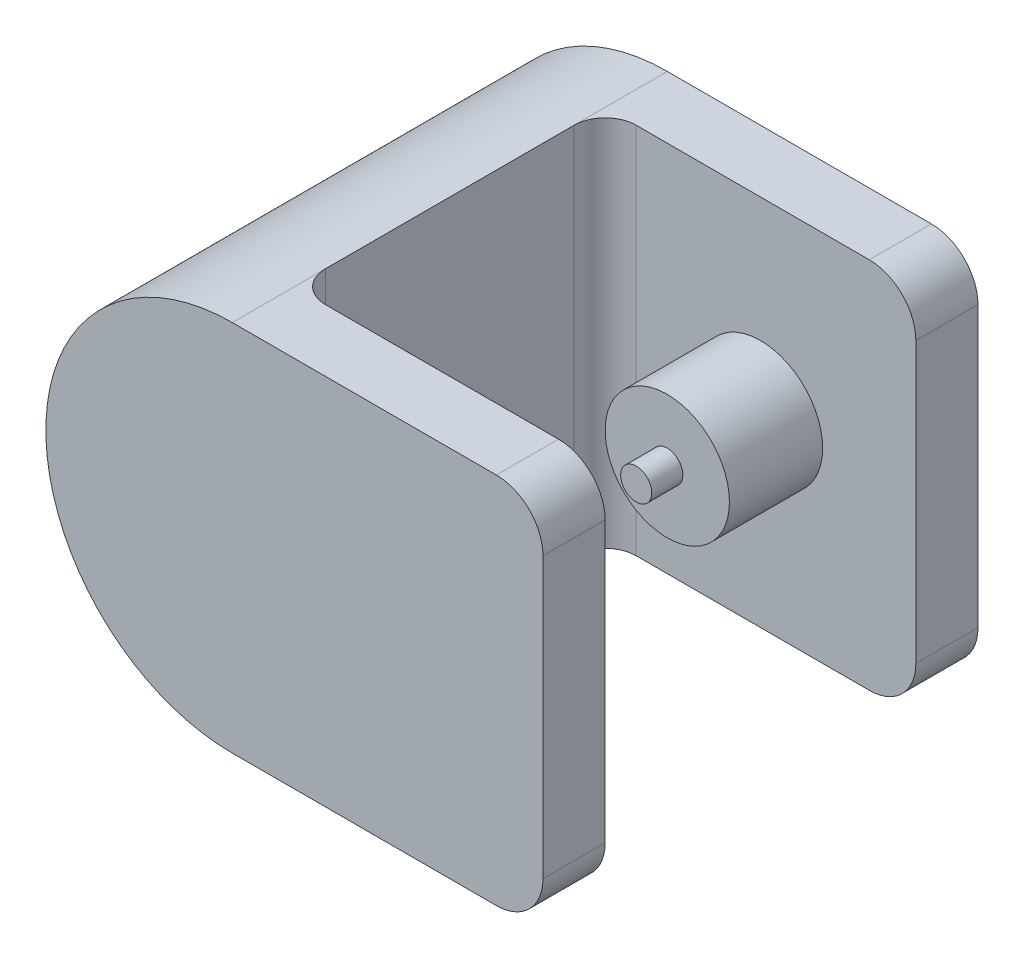
SolidWorks part; units mm, degrees
ref_plane "Ön Düzlem" through (0, 0, 0) normal (0, 0, 1) x (1, 0, 0)
ref_plane "Üst Düzlem" through (0, 0, 0) normal (0, 1, 0) x (1, 0, 0)
ref_plane "Sağ Düzlem" through (0, 0, 0) normal (1, 0, 0) x (0, 0, -1)
sketch "Çizim1" plane through (0, 0, 0) normal (0, 0, 1) x (1, 0, 0)
  line L1 (-50, -60) -> (50, -60)
  line L2 (-50, -60) -> (-50, 60)
  line L3 (-50, 60) -> (50, 60)
  line L4 (50, -60) -> (50, 60)
  line L5 (-50, -60) -> (50, 60) construction
  line L6 (-50, 60) -> (50, -60) construction
  arc A0 (-50, 60) -> (-50, -60) centre (-50, 0) ccw
  point P0 (0, 0)
  dimension "D1" = 120
  dimension "D2" = 100
extrude "Yükseklik-Ekstrüzyon1" add sketch "Çizim1" along normal blind 20 contours L1 L4 L3 L2 region at (0, 0, 0)
extrude "Yükseklik-Ekstrüzyon2" add sketch "Çizim1<3>" along normal blind 120 contours L2 A0 region at (-75.4648, 0, 0)
sketch "Çizim1<3>" plane through (0, 0, 0) normal (0, 0, 1) x (1, 0, 0) same geometry as "Çizim1"
sketch "Çizim2" plane through (0, 0, 120) normal (0, 0, 1) x (1, 0, 0)
  line L3 (-50, -60) -> (50, -60)
  line L4 (50, 60) -> (-50, 60)
  line L5 (50, -60) -> (50, 60)
  line L6 (-50, -60) -> (50, -60)
  line L7 (50, 60) -> (-50, 60)
  line L8 (50, -60) -> (50, 60)
  arc A1 (-50, 60) -> (-50, -60) centre (-50, 0) ccw
  arc A2 (-50, 60) -> (-50, -60) centre (-50, 0) ccw
  dimension "D1" = 0
extrude "Yükseklik-Ekstrüzyon3" add sketch "Çizim2" along normal blind 20 contours L6 L8 L7 A2
fillet "Radyus1" radius 10 2 edges at (-50, 0, 20) (-50, 0, 120)
fillet "Radyus2" radius 15 4 edges at (50, 60, 130) (50, -60, 130) (50, 60, 10) (50, -60, 10)
sketch "Çizim3" plane through (0, 0, 20) normal (0, 0, 1) x (1, 0, 0)
  circle A0 centre (0, 0) radius 20
  dimension "D1" = 40
extrude "Yükseklik-Ekstrüzyon4" add sketch "Çizim3" along normal blind 30
sketch "Çizim4" plane through (0, 0, 50) normal (0, 0, 1) x (1, 0, 0)
  circle A0 centre (0, 0) radius 5
  dimension "D1" = 10
extrude "Yükseklik-Ekstrüzyon5" add sketch "Çizim4" along normal blind 10 contours A0
sketch "Çizim5" plane through (0, 0, 120) normal (0, 0, -1) x (1, 0, 0)
  circle A0 centre (0, 0) radius 20
  dimension "D1" = 40
extrude "Yükseklik-Ekstrüzyon6" add sketch "Çizim5" along normal blind 30 contours A0
sketch "Çizim6" plane through (0, 0, 90) normal (0, 0, -1) x (1, 0, 0)
  circle A0 centre (0, 0) radius 5
  dimension "D1" = 10
extrude "Yükseklik-Ekstrüzyon7" add sketch "Çizim6" along normal blind 10
